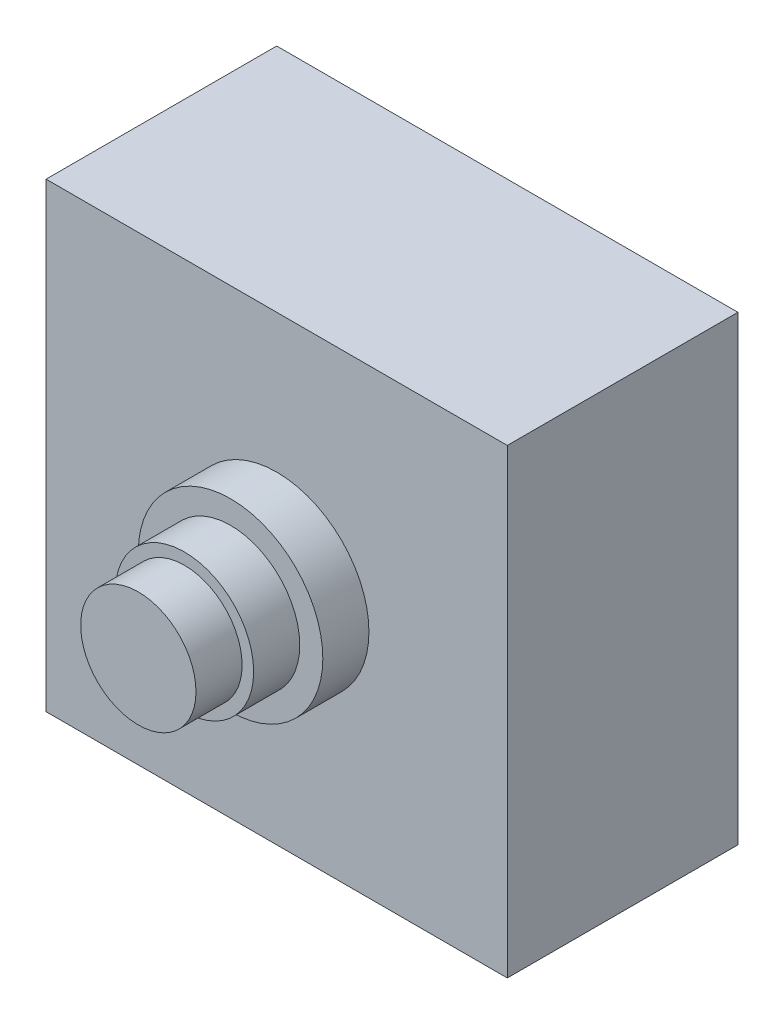
SolidWorks part; units mm, degrees
ref_plane "前视基准面" through (0, 0, 0) normal (0, 0, 1) x (1, 0, 0)
ref_plane "上视基准面" through (0, 0, 0) normal (0, 1, 0) x (1, 0, 0)
ref_plane "右视基准面" through (0, 0, 0) normal (1, 0, 0) x (0, 0, -1)
other "Configuration Table"
sketch "Sketch1" plane through (0, 0, 0) normal (0, 0, 1) x (1, 0, 0)
  line L1 (-100, -100) -> (100, -100)
  line L2 (-100, -100) -> (-100, 100)
  line L3 (-100, 100) -> (100, 100)
  line L4 (100, -100) -> (100, 100)
  line L5 (-100, -100) -> (100, 100) construction
  line L6 (-100, 100) -> (100, -100) construction
  point P0 (0, 0)
extrude "Boss-Extrude1" add sketch "Sketch1" along normal blind 100
ref_plane "Plane1" through (0, 0, 100) normal (0, 0, 1) x (1, 0, 0)
sketch "Sketch2" plane through (0, 0, 100) normal (0, 0, 1) x (1, 0, 0)
  circle A0 centre (0, 0) radius 40
extrude "Boss-Extrude2" add sketch "Sketch2" along normal blind 20
ref_plane "Plane2" through (0, 0, 120) normal (0, 0, 1) x (1, 0, 0)
sketch "Sketch3" plane through (0, 0, 120) normal (0, 0, 1) x (1, 0, 0)
  circle A0 centre (0, 0) radius 30
extrude "Boss-Extrude3" add sketch "Sketch3" along normal blind 20
ref_plane "Plane3" through (0, 0, 140) normal (0, 0, 1) x (1, 0, 0)
sketch "Sketch4" plane through (0, 0, 140) normal (0, 0, 1) x (1, 0, 0)
  circle A0 centre (0, 0) radius 25
extrude "Boss-Extrude4" add sketch "Sketch4" along normal blind 20
ref_plane "mount_face_bottom" through (0, 0, 0) normal (0, 0, 1) x (1, 0, 0)
ref_plane "top_face_main" through (0, 0, 160) normal (0, 0, 1) x (1, 0, 0)
sketch3d "3DSketch1"
  line L0 (0, 0, 0) -> (0, 0, 160) construction
ref_axis "main_axis_z" through (0, 0, 0) along (0, 0, 1)
